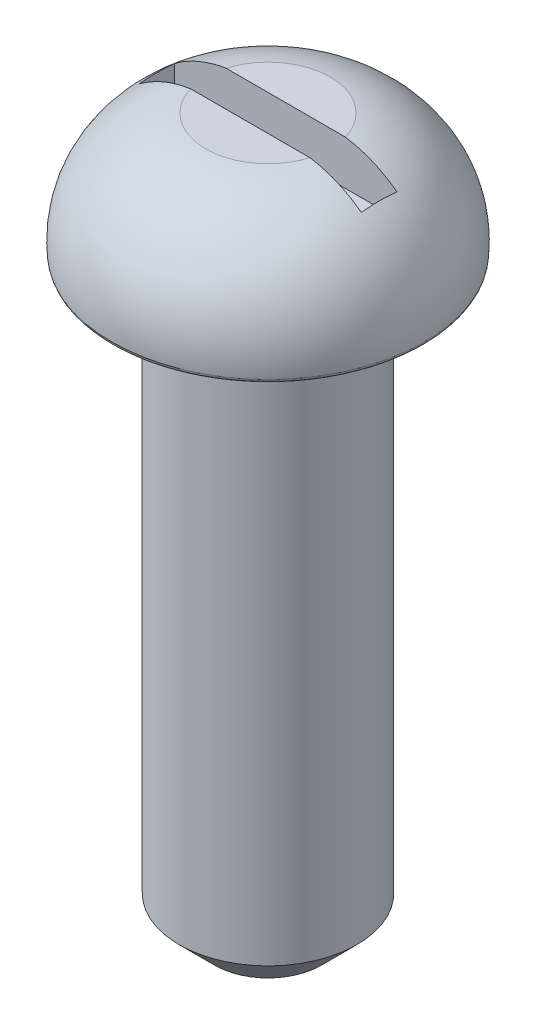
SolidWorks part; units mm, degrees
ref_plane "Спереди" through (0, 0, 0) normal (0, 0, 1) x (1, 0, 0)
ref_plane "Сверху" through (0, 0, 0) normal (0, 1, 0) x (1, 0, 0)
ref_plane "Справа" through (0, 0, 0) normal (1, 0, 0) x (0, 0, -1)
sketch "Эскиз1" plane through (0, 0, 0) normal (0, 0, 1) x (1, 0, 0)
  line L0 (3.5, 13.2) -> (2, 13.2)
  line L1 (0, 0) -> (0, 16)
  line L2 (2, 13.2) -> (2, 0.8)
  line L3 (2, 0.8) -> (1.2, 0)
  line L4 (1.2, 0) -> (0, 0)
  line L5 (0, 16) -> (1.4, 16)
  arc A0 (1.4, 16) -> (3.5, 13.2) centre (1, 13.5125) cw
  dimension "D2" = 1.4
  dimension "D8" = 1
  dimension "D1" = 16
  dimension "D3" = 2
  dimension "D4" = 1.2
  dimension "D5" = 2.8
  dimension "D6" = 3.5
  dimension "D7" = 45
revolve "Повернуть1" add sketch "Эскиз1" angle 360 about L1
fillet "Скругление1" radius 0.1 1 edges at (0, 13.2, -3.5)
sketch "Эскиз3" plane through (0, 16, 0) normal (0, 1, 0) x (-1, 0, 0)
  line L1 (2.5, -0.4) -> (-2.5, -0.4)
  line L2 (2.5, -0.4) -> (2.5, 0.4)
  line L3 (2.5, 0.4) -> (-2.5, 0.4)
  line L4 (-2.5, -0.4) -> (-2.5, 0.4)
  dimension "D1" = 0.8
  dimension "D2" = 0.4
  dimension "D3" = 5
  dimension "D4" = 2.5
extrude "Вырез-Вытянуть2" cut sketch "Эскиз3" against normal blind 1
ref_axis "Ось1" through (0, -9.8623, 0) along (0, 1, 0)
